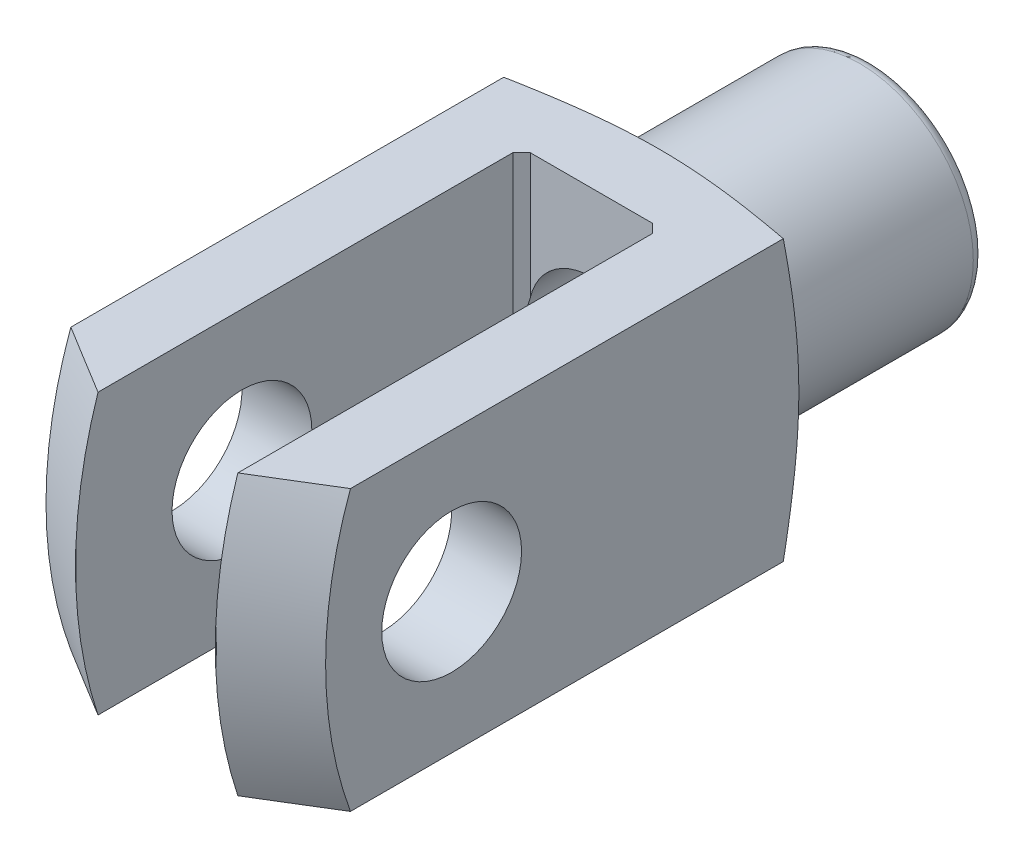
SolidWorks part; units mm, degrees
ref_plane "Front Plane" through (0, 0, 0) normal (0, 0, 1) x (1, 0, 0)
ref_plane "Top Plane" through (0, 0, 0) normal (0, 1, 0) x (1, 0, 0)
ref_plane "Right Plane" through (0, 0, 0) normal (1, 0, 0) x (0, 0, -1)
ref_plane "Plane1" through (0, 0, 0) normal (1, 0, 0) x (0, 0, -1)
sketch "Sketch1" plane through (0, 0, 0) normal (1, 0, 0) x (0, 0, -1)
  line L0 (-19, 0) -> (-19, 32)
  line L1 (-19, 32) -> (35.4449, 32)
  line L2 (35.4449, 32) -> (40, 15)
  line L3 (42, 13) -> (62.7, 13)
  line L4 (64, 11.7) -> (64, 0)
  line L5 (64, 0) -> (-19, 0)
  line L6 (64, 0) -> (-19, 0) construction
  arc A0 (40, 15) -> (42, 13) centre (42, 15) ccw
  arc A1 (62.7, 13) -> (64, 11.7) centre (62.7, 11.7) cw
revolve "Revolve1" add sketch "Sketch1" angle 360 about L6 reverse direction yes
ref_plane "Plane2" through (0, 0, 0) normal (0, 1, 0) x (1, 0, 0)
sketch "Sketch2" plane through (0, 0, 0) normal (0, 1, 0) x (1, 0, 0)
  line L0 (-8, 31) -> (-8, -20)
  line L1 (-8, -20) -> (8, -20)
  line L2 (8, -20) -> (8, 31)
  line L3 (8, 31) -> (7, 32)
  line L4 (7, 32) -> (-7, 32)
  line L5 (-7, 32) -> (-8, 31)
extrude "Cut-Extrude1" cut sketch "Sketch2" against normal blind 33 and the other way blind 33
ref_plane "Plane3" through (0, 0, 0) normal (1, 0, 0) x (0, 0, -1)
sketch "Sketch3" plane through (0, 0, 0) normal (1, 0, 0) x (0, 0, -1)
  line L0 (-52, -48) -> (64, -48)
  line L1 (64, -48) -> (64, -16)
  line L2 (64, -16) -> (-20, -16)
  line L3 (-20, -16) -> (-20, 16)
  line L4 (-20, 16) -> (64, 16)
  line L5 (64, 16) -> (64, 48)
  line L6 (64, 48) -> (-52, 48)
  line L7 (-52, 48) -> (-52, -48)
extrude "Cut-Extrude2" cut sketch "Sketch3" against normal blind 33 and the other way blind 33
ref_plane "Plane4" through (0, 0, 0) normal (0, 1, 0) x (1, 0, 0)
sketch "Sketch4" plane through (0, 0, 0) normal (0, 1, 0) x (1, 0, 0)
  line L0 (-48, -52) -> (48, -52)
  line L1 (48, -52) -> (48, 64)
  line L2 (48, 64) -> (16, 64)
  line L3 (16, 64) -> (16, -20)
  line L4 (16, -20) -> (-16, -20)
  line L5 (-16, -20) -> (-16, 64)
  line L6 (-16, 64) -> (-48, 64)
  line L7 (-48, 64) -> (-48, -52)
extrude "Cut-Extrude3" cut sketch "Sketch4" against normal blind 33 and the other way blind 33
ref_plane "Plane5" through (0, 0, 0) normal (0, 0, 1) x (1, 0, 0)
sketch "Sketch5" plane through (0, 0, 0) normal (0, 0, 1) x (1, 0, 0)
  line L0 (-19.75, 0) -> (-19.75, 8)
  line L1 (-19.75, 8) -> (19.75, 8)
  line L2 (19.75, 8) -> (19.75, 0)
  line L3 (19.75, 0) -> (-19.75, 0)
  line L4 (19.75, 0) -> (-19.75, 0) construction
revolve "Cut-Revolve1" cut sketch "Sketch5" angle 360 about L4 reverse direction yes
ref_plane "Plane6" through (0, 0, 0) normal (1, 0, 0) x (0, 0, -1)
sketch "Sketch6" plane through (0, 0, 0) normal (1, 0, 0) x (0, 0, -1)
  line L0 (30.9, 0) -> (30.9, 7.188)
  line L1 (30.9, 7.188) -> (63.288, 7.188)
  line L2 (63.288, 7.188) -> (64.1, 8)
  line L3 (64.1, 8) -> (64.1, 0)
  line L4 (64.1, 0) -> (30.9, 0)
  line L5 (64.1, 0) -> (30.9, 0) construction
revolve "Cut-Revolve2" cut sketch "Sketch6" angle 360 about L5 reverse direction yes
cosmetic thread "Cosmetic Thread1" parameters "D1"=28.2, "D2"=16
ref_plane "Plane7" through (0, 0, 0) normal (0, 1, 0) x (1, 0, 0)
sketch "Sketch7" plane through (0, 0, 0) normal (0, 1, 0) x (1, 0, 0)
  line L0 (-19, -49.6418) -> (0, -60.6115)
  line L1 (0, -60.6115) -> (19, -49.6418)
  line L2 (19, -49.6418) -> (19, -12.6914)
  line L3 (19, -12.6914) -> (0, -23.6611)
  line L4 (0, -23.6611) -> (-19, -12.6914)
  line L5 (-19, -12.6914) -> (-19, -49.6418)
  line L6 (-19, 32) -> (19, 32) construction
revolve "Cut-Revolve3" cut sketch "Sketch7" angle 90 about L6 other way angle 90 reverse direction yes
